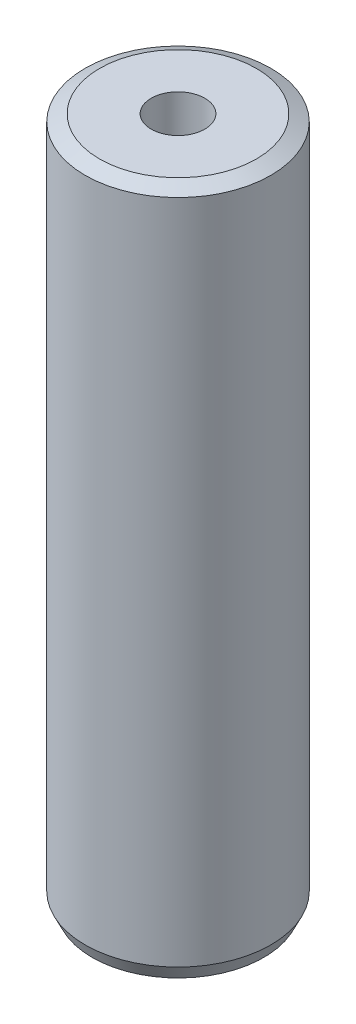
SolidWorks part; units mm, degrees
ref_plane "Front Plane" through (0, 0, 0) normal (0, 0, 1) x (1, 0, 0)
ref_plane "Top Plane" through (0, 0, 0) normal (0, 1, 0) x (1, 0, 0)
ref_plane "Right Plane" through (0, 0, 0) normal (1, 0, 0) x (0, 0, -1)
sketch "Sketch1" plane through (0, 0, 0) normal (0, 1, 0) x (1, 0, 0)
  circle A0 centre (0, 0) radius 12.5
  dimension "SHAFT_OD" = 25
extrude "Boss-Extrude1" add sketch "Sketch1" along normal blind 92.6309
sketch "Sketch2" plane through (0, 0, 0) normal (0, 1, 0) x (1, 0, 0)
  circle A0 centre (0, 0) radius 3.6115
  dimension "BORE_D" = 7.2231
extrude "Cut-Extrude1" cut sketch "Sketch2" along normal through all
chamfer "Chamfer1" distance 0.9426 angle 64.043 2 edges at (0, 92.6309, 12.5) (0, 0, 12.5) first distance on face at (0, 92.6309, 12.5) first distance on face at (0, 0, 3.6115)
